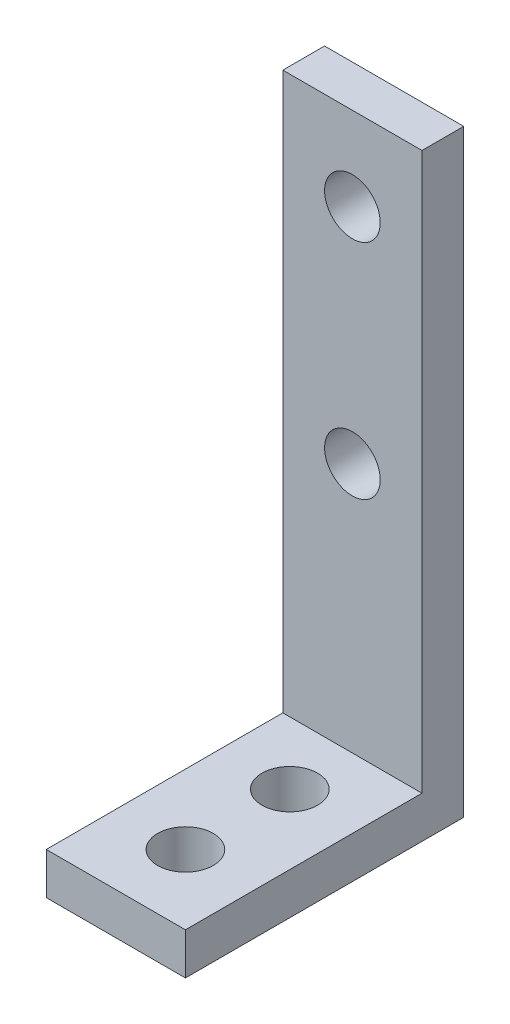
SolidWorks part; units mm, degrees
ref_plane "Front Plane" through (0, 0, 0) normal (0, 0, 1) x (1, 0, 0)
ref_plane "Top Plane" through (0, 0, 0) normal (0, 1, 0) x (1, 0, 0)
ref_plane "Right Plane" through (0, 0, 0) normal (1, 0, 0) x (0, 0, -1)
sketch "Sketch2" plane through (0, 0, 0) normal (0, 1, 0) x (1, 0, 0)
  line L1 (-5, -10) -> (5, -10)
  line L2 (-5, -10) -> (-5, 10)
  line L3 (-5, 10) -> (5, 10)
  line L4 (5, -10) -> (5, 10)
  line L5 (-5, -10) -> (5, 10) construction
  line L6 (-5, 10) -> (5, -10) construction
  point P0 (0, 0)
  dimension "D1" = 10
  dimension "D2" = 20
extrude "Boss-Extrude1" add sketch "Sketch2" along normal blind 3
sketch "Sketch4" plane through (0, 3, 0) normal (0, 1, 0) x (1, 0, 0)
  line L0 (-5, 10) -> (-5, -10) construction
  line L1 (5, 10) -> (-5, 10)
  line L2 (5, 10) -> (5, 7)
  line L3 (5, 7) -> (-5, 7)
  line L4 (-5, 10) -> (-5, 7)
  dimension "D1" = 3
extrude "Boss-Extrude2" add sketch "Sketch4" along normal blind 40
sketch "Sketch6" plane through (0, 3, 0) normal (0, 1, 0) x (1, 0, 0)
  line L0 (-5, 7) -> (-5, -10) construction
  line L1 (-5, -10) -> (5, -10) construction
  circle A0 centre (0, 2.5) radius 2
  circle A1 centre (0, -5) radius 2
  dimension "D4" = 4
  dimension "D5" = 4
  dimension "D1" = 5
  dimension "D2" = 5
  dimension "D3" = 5
  dimension "D6" = 7.5
extrude "Cut-Extrude1" cut sketch "Sketch6" against normal through all
sketch "Sketch7" plane through (0, 0, -7) normal (0, 0, 1) x (1, 0, 0)
  line L1 (5, 43) -> (5, 3) construction
  line L3 (-5, 43) -> (5, 43) construction
  circle A0 centre (0, 37) radius 2
  circle A1 centre (0, 21) radius 2
  point P4 (0, 0)
  dimension "D3" = 4
  dimension "D4" = 4
  dimension "D1" = 5
  dimension "D2" = 5
  dimension "D5" = 16
  dimension "D6" = 6
extrude "Cut-Extrude2" cut sketch "Sketch7" against normal through all
